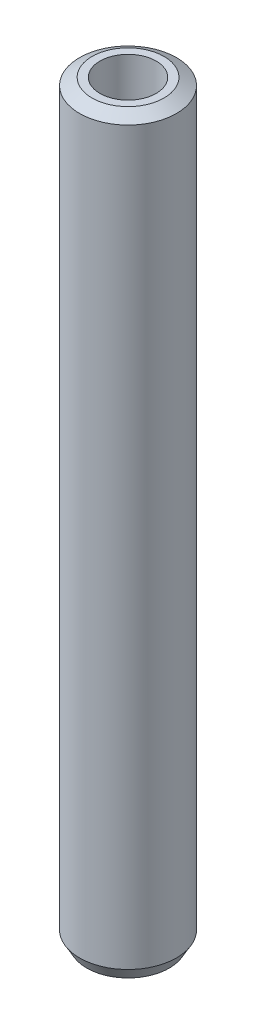
SolidWorks part; units mm, degrees
ref_plane "Front Plane" through (0, 0, 0) normal (0, 0, 1) x (1, 0, 0)
ref_plane "Top Plane" through (0, 0, 0) normal (0, 1, 0) x (1, 0, 0)
ref_plane "Right Plane" through (0, 0, 0) normal (1, 0, 0) x (0, 0, -1)
sketch "Sketch1" plane through (0, 0, 0) normal (0, 1, 0) x (1, 0, 0)
  circle A0 centre (0, 0) radius 37.5
  dimension "SHAFT_OD" = 75
extrude "Boss-Extrude1" add sketch "Sketch1" along normal blind 581.0801
sketch "Sketch2" plane through (0, 0, 0) normal (0, 1, 0) x (1, 0, 0)
  circle A0 centre (0, 0) radius 21.7387
  dimension "BORE_D" = 43.4773
extrude "Cut-Extrude1" cut sketch "Sketch2" along normal through all
chamfer "Chamfer1" distance 5.5581 angle 60 2 edges at (0, 581.0801, 37.5) (0, 0, 37.5) first distance on face at (0, 581.0801, 37.5) first distance on face at (0, 0, 21.7387)
